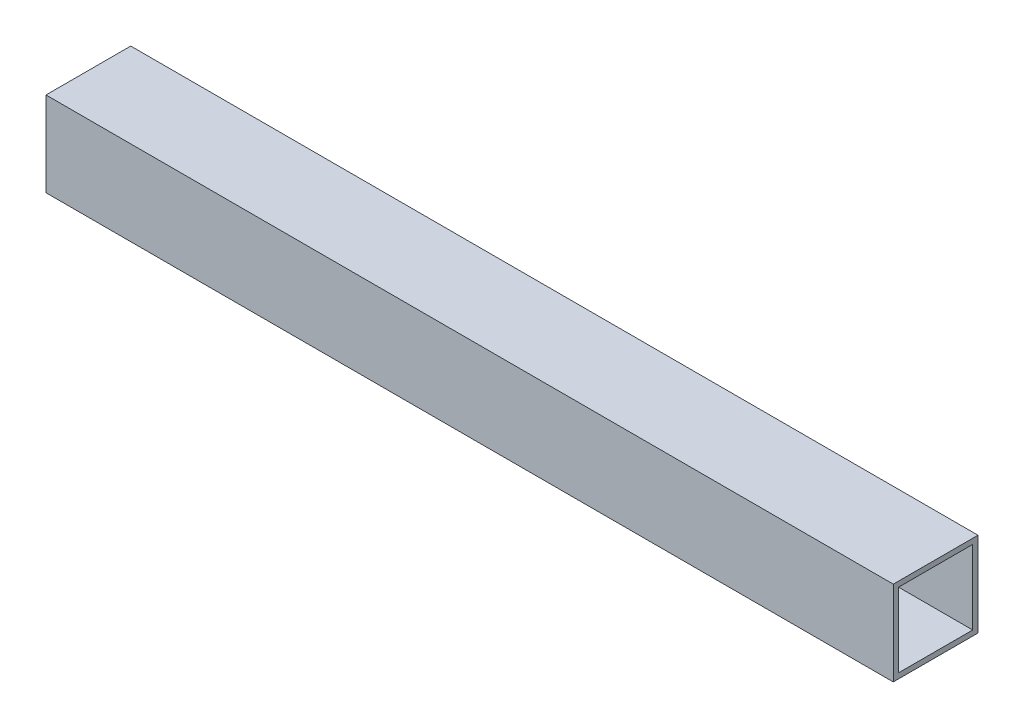
SolidWorks part; units mm, degrees
ref_plane "Front" through (0, 0, 0) normal (0, 0, 1) x (1, 0, 0)
ref_plane "Top" through (0, 0, 0) normal (0, 1, 0) x (1, 0, 0)
ref_plane "Right" through (0, 0, 0) normal (1, 0, 0) x (0, 0, -1)
sketch "Sketch1" plane through (0, 0, 0) normal (1, 0, 0) x (0, 0, -1)
  line L1 (-12.7, -12.7) -> (12.7, -12.7)
  line L2 (-12.7, -12.7) -> (-12.7, 12.7)
  line L3 (-12.7, 12.7) -> (12.7, 12.7)
  line L4 (12.7, -12.7) -> (12.7, 12.7)
  line L5 (-12.7, -12.7) -> (12.7, 12.7) construction
  line L6 (-12.7, 12.7) -> (12.7, -12.7) construction
  point P0 (0, 0)
  dimension "D1" = 25.4
extrude "Extrude-Thin1" add sketch "Sketch1" along normal blind 254 thin thin type one direction reverse wall 1.5875
